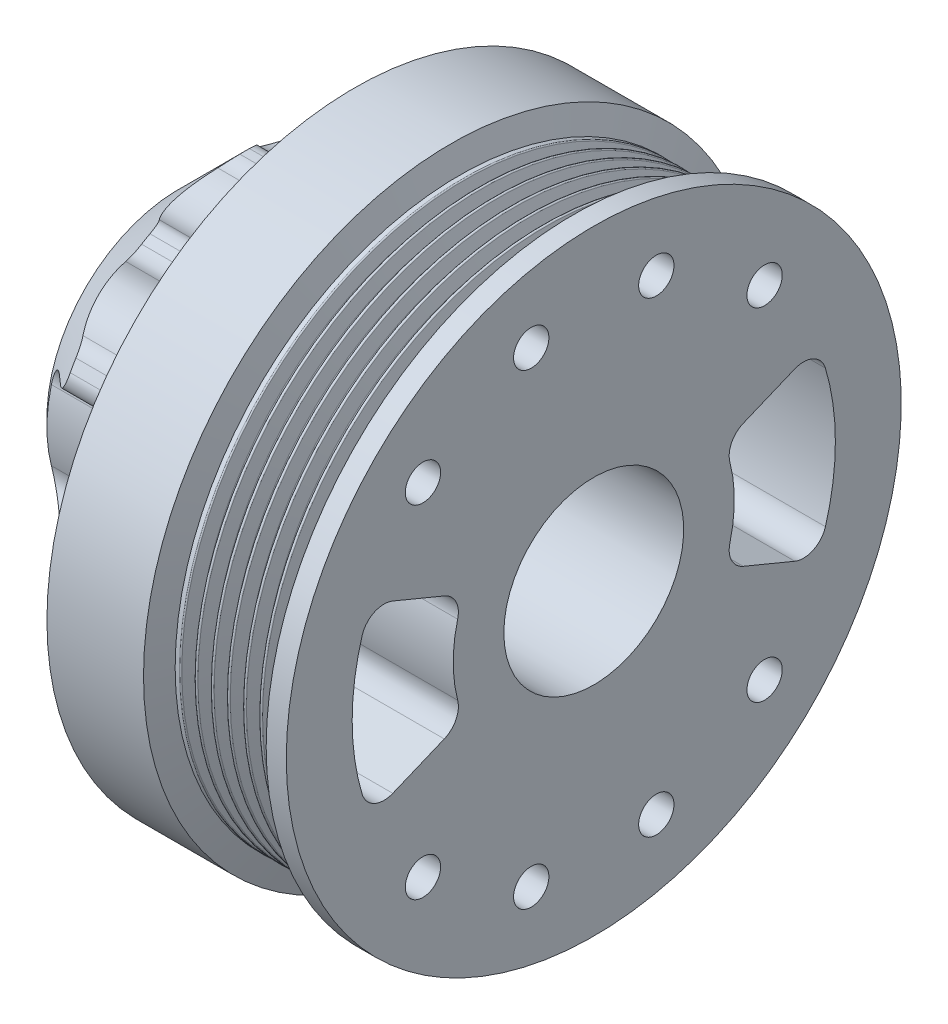
SolidWorks part; units mm, degrees
material "6061-T6 (SS)"
ref_plane "Front Plane" through (0, 0, 0) normal (0, 0, 1) x (1, 0, 0)
ref_plane "Top Plane" through (0, 0, 0) normal (0, 1, 0) x (1, 0, 0)
ref_plane "Right Plane" through (0, 0, 0) normal (1, 0, 0) x (0, 0, -1)
sketch "Sketch1" plane through (0, 0, 0) normal (0, 0, 1) x (1, 0, 0)
  line L0 (0, 0) -> (106.255, 0) construction
  line L1 (-19.05, 13) -> (40.95, 13)
  line L2 (40.95, 13) -> (40.95, 44.45)
  line L3 (40.95, 44.45) -> (6.35, 44.45)
  line L4 (6.35, 44.45) -> (6.35, 28.575)
  line L5 (6.35, 28.575) -> (-19.05, 28.575)
  line L6 (-19.05, 28.575) -> (-19.05, 13)
  dimension "D1" = 34.6
  dimension "D2" = 88.9
  dimension "D3" = 26
  dimension "D4" = 25.4
  dimension "D5" = 57.15
  dimension "D6" = 19.05
revolve "Revolve1" add sketch "Sketch1" angle 360 about L0
sketch "Sketch3" plane through (-19.05, 0, 0) normal (-1, 0, 0) x (0, 0, 1)
  line L0 (0, 0) -> (9.0393, 33.735) construction
  line L1 (0, 0) -> (0, 49.6351) construction
  arc A0 (2.2542, 28.4859) -> (12.2907, 25.7967) centre (8.2175, 30.6681) ccw
  circle A1 centre (0, 0) radius 28.575 construction
  arc A2 (12.2907, 25.7967) -> (2.2542, 28.4859) centre (0, 0) ccw
  point P6 (6.574, 24.5345)
  point P10 (7.3958, 27.6013)
  dimension "D1" = 34.925
  dimension "D2" = 3.175
  dimension "D3" = 6.35
  dimension "D4" = 15
extrude "Cut-Extrude1" cut sketch "Sketch3" against normal up to surface (25.4 mm away) up to face at (6.35, 0, 28.575)
fillet "Fillet1" radius 2.54 2 edges at (-6.35, 25.7967, 12.2907) (-6.35, 28.4859, 2.2542)
sketch "Sketch6" plane through (6.35, 0, 0) normal (-1, 0, 0) x (0, 0, 1)
  point P0 (9.0393, 33.735)
hole_wizard "1/4-20 Tapped Hole1" positions "Sketch7" profile "Sketch9" tap size "1/4-20" standard "ANSI Inch" end condition through all
sketch "Sketch7" plane through (6.35, 0, 0) normal (-1, 0, 0) x (0, 0, 1)
  point P0 (9.0393, 33.735)
sketch "Sketch9" plane through (6.35, 33.735, 9.0393) normal (0, 1, 0) x (0, 0, 1)
  line L0 (0, 0) -> (0, 34.6)
  line L1 (0, 34.6) -> (2.5527, 34.6)
  line L2 (2.5527, 34.6) -> (2.5527, 0)
  line L5 (2.5527, 0) -> (0, 0)
  line L11 (0, -6.35) -> (0, 107.95) construction
  dimension "Thru Tap Drill Dia." = 5.1054
  dimension "Thru Tap Drill Depth" = 34.6
pattern_circular "CirPattern1" count 12 over 360 about axis through (6.35, 0, 0) along (-1, 0, 0) skipping 3, 4, 9, 10 of "Cut-Extrude1", "Fillet1", "1/4-20 Tapped Hole1"
sketch "Sketch10" plane through (0, 0, 0) normal (0, 0, 1) x (1, 0, 0)
  line L0 (40.95, 44.45) -> (6.35, 44.45) construction
  line L2 (35.9966, 40.9635) -> (35.401, 39.3272)
  line L3 (34.6372, 39.3272) -> (34.0416, 40.9635)
  line L9 (36.1875, 44.45) -> (33.8507, 44.45)
  line L10 (40.95, 44.45) -> (6.35, 44.45) construction
  line L11 (34.0416, 40.9635) -> (35.9966, 40.9635) construction
  line L12 (0, 0) -> (72.0631, 0) construction
  line L13 (36.1875, 41.0972) -> (36.1875, 44.45)
  line L14 (33.8507, 41.0972) -> (33.8507, 44.45)
  line L15 (33.2905, 39.0598) -> (37.1262, 39.0598) construction
  line L16 (32.9874, 42.291) -> (37.178, 42.291) construction
  arc A0 (34.6372, 39.3272) -> (35.401, 39.3272) centre (35.0191, 39.4662) ccw
  arc A1 (35.9966, 40.9635) -> (36.1875, 41.0972) centre (36.1875, 40.894) cw
  arc A2 (34.0416, 40.9635) -> (33.8507, 41.0972) centre (33.8507, 40.894) ccw
  dimension "D4" = 4.7625
  dimension "D2" = 40
  dimension "D5" = 2.0374
  dimension "D6" = 2.3368
  dimension "D7" = 42.291
  dimension "D8" = 1.1938
ref_axis "Axis1" through (40.95, 0, 0) along (-1, 0, 0)
revolve "Cut-Revolve1" cut sketch "Sketch10" angle 360 about axis through (40.95, 0, 0) along (-1, 0, 0)
pattern_linear "LPattern2" count 6 spacing 2.3368 along (-1, 0, 0) of "Cut-Revolve1"
sketch "Sketch23" plane through (0, 0, 0) normal (0, 0, 1) x (1, 0, 0)
  line L0 (36.1875, 41.0972) -> (36.8225, 41.0972)
  line L1 (36.8225, 41.0972) -> (38.0428, 44.45)
  line L2 (40.95, 44.45) -> (36.1875, 44.45) construction
  line L3 (38.0428, 44.45) -> (36.1875, 44.45)
  line L4 (36.1875, 44.45) -> (36.1875, 41.0972)
  line L5 (35.0191, 39.0598) -> (35.0191, 41.518) construction
  line L6 (29.1771, 41.0972) -> (29.1771, 44.846) construction
  line L7 (22.1667, 44.45) -> (22.1667, 41.0972)
  line L8 (20.3114, 44.45) -> (22.1667, 44.45)
  line L9 (21.5317, 41.0972) -> (20.3114, 44.45)
  line L10 (22.1667, 41.0972) -> (21.5317, 41.0972)
  line L11 (40.95, 44.45) -> (36.1875, 44.45) construction
  arc A0 (34.6372, 39.3272) -> (35.401, 39.3272) centre (35.0191, 39.4662) ccw construction
  arc A1 (29.368, 40.9635) -> (28.9862, 40.9635) centre (29.1771, 40.894) ccw construction
  dimension "D1" = 1.8034
  dimension "D2" = 20
revolve "Cut-Revolve3" cut sketch "Sketch23" angle 360 about axis through (40.95, 0, 0) along (-1, 0, 0)
sketch "Sketch11" plane through (0, 0, 0) normal (0, 1, 0) x (1, 0, 0)
  line L1 (6.35, 44.45) -> (-19.05, 44.45)
  line L2 (-19.05, 44.45) -> (-19.05, 19.05)
  line L3 (-19.05, 13) -> (-19.05, -13) construction
  line L4 (0, 0) -> (-37.8551, 0) construction
  line L5 (-19.05, 19.05) -> (6.35, 44.45)
  line L11 (6.35, -6.4866) -> (6.35, -11.592) construction
  point P13 (-19.05, 28.575)
  dimension "D1" = 9.525
  dimension "D2" = 45
revolve "Cut-Revolve2" cut sketch "Sketch11" angle 360 about L4
sketch "Sketch25" plane through (-19.05, 0, 0) normal (-1, 0, 0) x (0, 0, 1)
  line L0 (18.7732, 7.7761) -> (32.2665, 13.3652)
  line L1 (18.7732, -7.7761) -> (32.2665, -13.3652)
  line L2 (0, 0) -> (34.925, 0) construction
  arc A0 (18.7732, 7.7761) -> (18.7732, -7.7761) centre (0, 0) cw
  arc A1 (32.2665, 13.3652) -> (32.2665, -13.3652) centre (0, 0) cw
  dimension "D1" = 20.32
  dimension "D2" = 34.925
  dimension "D3" = 45
extrude "Cut-Extrude2" cut sketch "Sketch25" against normal through all
fillet "Fillet2" radius 3.302 4 edges at (23.65, -13.3652, 32.2665) (23.65, 13.3652, 32.2665) (11.585, -7.7761, 18.7732) (11.585, 7.7761, 18.7732)
mirror "Mirror1" about plane through (0, 0, 0) normal (0, 0, 1) of "Fillet2", "Cut-Extrude2"
fillet "Fillet3" radius 2.54 4 edges at (-1.5875, 10.9352, -26.3999) (-1.5875, -10.9352, -26.3999) (-1.5875, -10.9352, 26.3999) (-1.5875, 10.9352, 26.3999)
equation "\"D7@Sketch10\"=3.33in/2"
equation "\"D8@Sketch10\"=.094/2"
